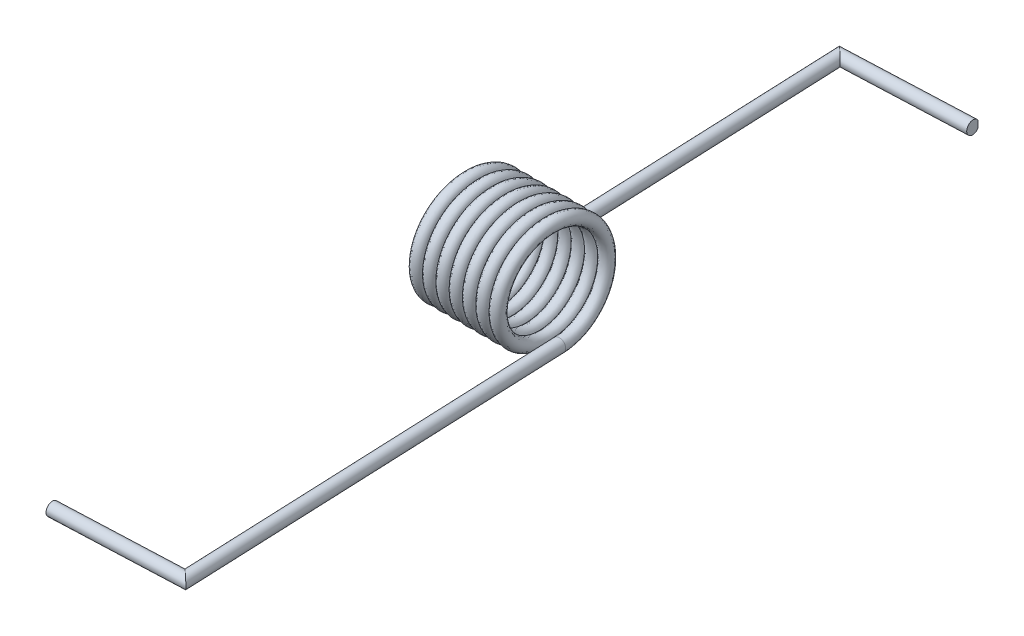
SolidWorks part; units mm, degrees
note: The reader was unsure of these and kept them because the rebuilt part matched: shared geometry of "Sketch16<4>".
ref_plane "Front" through (0, 0, 0) normal (0, 0, 1) x (1, 0, 0)
ref_plane "Top" through (0, 0, 0) normal (0, 1, 0) x (1, 0, 0)
ref_plane "Right" through (0, 0, 0) normal (1, 0, 0) x (0, 0, -1)
sketch "Sketch1" plane through (0, 0, 0) normal (1, 0, 0) x (0, 0, -1)
  line L0 (0, 0) -> (0, -2.2098) construction
  line L1 (0, -2.2098) -> (0, -2.5273) construction
  line L2 (0, -2.5273) -> (0, -2.8448) construction
  circle A0 centre (0, 0) radius 2.2098 construction
  circle A1 centre (0, 0) radius 2.8448 construction
  circle A2 centre (0, 0) radius 2.5273
  circle A3 centre (0, -2.5273) radius 0.3175 construction
  circle A4 centre (0, 0) radius 1.778 construction
curve "Helix/Spiral1" pitch 0.6604 height 4.6228 turns 7
ref_plane "Plane1" through (0, -2.5273, 0) normal (-0.0416, 0, -0.9991) x (-0.9991, 0, 0.0416)
sketch "Sketch2" plane through (0, -2.5273, 0) normal (-0.0416, 0, -0.9991) x (-0.9991, 0, 0.0416)
  circle A0 centre (0, 0) radius 0.3175
sweep "Sweep1" add profiles "Sketch2" path "Helix/Spiral1"
sketch "Sketch3" plane through (0, 0, 0) normal (0.0416, 0, 0.9991) x (0.9991, 0, -0.0416)
  circle A1 centre (0, -2.5273) radius 0.3175
  circle A2 centre (0, -2.5273) radius 0.3175
  dimension "D1" = 0
extrude "Extrude1" add sketch "Sketch3" along normal blind 19.05
sketch "Sketch4" plane through (-0.008, 0, -0.1919) normal (-0.0416, 0, -0.9991) x (-0.9955, -0.0856, 0.0414)
  circle A1 centre (4.8182, -2.1226) radius 0.3175
  circle A2 centre (4.8182, -2.1226) radius 0.3175
  dimension "D1" = 0
extrude "Extrude2" add sketch "Sketch4" along normal blind 19.05
sketch "Sketch7" plane through (0.7916, 0, 19.0335) normal (0.0416, 0, 0.9991) x (0.9991, 0, -0.0416)
  line L1 (0, -2.2098) -> (-6.35, -2.2098)
  line L2 (0, -2.2098) -> (0, -2.8448)
  line L3 (0, -2.8448) -> (-6.35, -2.8448)
  line L4 (-6.35, -2.2098) -> (-6.35, -2.8448)
  circle A0 centre (0, -2.5273) radius 0.3175 construction
  circle A1 centre (0, -2.5273) radius 0.3175 construction
  dimension "D1" = 6.35
extrude "Boss-Extrude1" add sketch "Sketch7" along normal blind 0.635
sketch "Sketch8" plane through (-6.3445, 0, 0.2639) normal (-0.9991, 0, 0.0416) x (0.0416, 0, 0.9991)
  line L2 (19.05, -2.2098) -> (19.685, -2.2098)
  line L3 (19.05, -2.2098) -> (19.05, -2.8448)
  line L4 (19.05, -2.8448) -> (19.685, -2.8448)
  line L5 (19.685, -2.2098) -> (19.685, -2.8448)
  circle A0 centre (19.3675, -2.5273) radius 0.3175
  line M1 (19.05, -2.2098) -> (19.05, -2.8448)
  line M2 (19.05, -2.8448) -> (19.685, -2.8448)
extrude "Cut-Extrude2" cut sketch "Sketch8" against normal up to surface (6.35 mm away) contours A0 L2 M1 | A0 L3 M2 up to face at (0.7916, -2.5273, 19.0335)
sketch "Sketch9" plane through (-6.3445, 0, 0.2639) normal (-0.9991, 0, 0.0416) x (0.0416, 0, 0.9991)
  line L0 (19.3675, -2.2098) -> (19.3675, -2.8448)
  line L1 (19.3675, -2.2098) -> (19.685, -2.2098)
  line L2 (19.685, -2.2098) -> (19.685, -2.8448)
  line L3 (19.685, -2.8448) -> (19.3675, -2.8448)
  circle A0 centre (19.3675, -2.5273) radius 0.3175
  line M2 (19.3675, -2.8448) -> (19.685, -2.8448)
  line M3 (19.685, -2.8448) -> (19.685, -2.2098)
  line M4 (19.685, -2.2098) -> (19.3675, -2.2098)
extrude "Cut-Extrude3" cut sketch "Sketch9" against normal through all contours A0 L2 M4 | A0 M2 M3
sketch "Sketch10" plane through (0.7916, 0, 19.0335) normal (0.0416, 0, 0.9991) x (0.9991, 0, -0.0416)
  line L0 (0, -2.8448) -> (0, -2.2098) construction
  line L1 (0, -2.2098) -> (0, -2.8448)
  circle A0 centre (0, -2.5273) radius 0.3175
  line M1 (0, -2.2098) -> (0, -2.8448)
  arc M2 (0, -2.8448) -> (0, -2.2098) centre (0, -2.5273) ccw
extrude "Boss-Extrude2" add sketch "Sketch10" along normal blind 0.635 contours M2 M1
sketch "Sketch11" plane through (0, 0, 0) normal (-0.9991, 0, 0.0416) x (0.0416, 0, 0.9991)
  line L2 (19.685, -2.5273) -> (19.685, -2.2098)
  line L3 (19.685, -2.2098) -> (19.3675, -2.2098)
  line L4 (19.685, -2.5273) -> (19.685, -2.2098)
  line L5 (19.685, -2.2098) -> (19.3675, -2.2098)
  arc A1 (19.685, -2.5273) -> (19.3675, -2.2098) centre (19.3675, -2.5273) ccw
  arc A2 (19.685, -2.5273) -> (19.3675, -2.2098) centre (19.3675, -2.5273) ccw
  dimension "D1" = 0
extrude "Cut-Extrude4" cut sketch "Sketch11" against normal blind 0.635
sketch "Sketch12" plane through (0, 0, 0) normal (-0.9991, 0, 0.0416) x (0.0416, 0, 0.9991)
  line L0 (19.685, -2.5273) -> (19.685, -2.8448) construction
  line L1 (19.685, -2.8448) -> (19.3675, -2.8448) construction
  line L2 (19.685, -2.5273) -> (19.685, -2.8448)
  line L3 (19.685, -2.8448) -> (19.3675, -2.8448)
  arc A0 (19.3675, -2.8448) -> (19.685, -2.5273) centre (19.3675, -2.5273) ccw construction
  arc A1 (19.3675, -2.8448) -> (19.685, -2.5273) centre (19.3675, -2.5273) ccw
extrude "Cut-Extrude5" cut sketch "Sketch12" against normal blind 0.635
sketch "Sketch13" plane through (-0.7996, 0, -19.2255) normal (-0.0416, 0, -0.9991) x (-0.9991, 0, 0.0416)
  line L1 (4.6188, -2.2098) -> (-1.7312, -2.2098)
  line L2 (4.6188, -2.2098) -> (4.6188, -2.8448)
  line L3 (4.6188, -2.8448) -> (-1.7312, -2.8448)
  line L4 (-1.7312, -2.2098) -> (-1.7312, -2.8448)
  circle A0 centre (4.6188, -2.5273) radius 0.3175 construction
  dimension "D1" = 6.35
extrude "Boss-Extrude3" add sketch "Sketch13" along normal blind 0.635
sketch "Sketch14" plane through (-0.7996, 0, -19.2255) normal (-0.0416, 0, -0.9991) x (-0.9991, 0, 0.0416)
  line L0 (4.6188, -2.8448) -> (4.6188, -2.2098) construction
  line L1 (4.6188, -2.8448) -> (4.6188, -2.2098)
  arc A0 (4.6188, -2.8448) -> (4.6188, -2.2098) centre (4.6188, -2.5273) ccw construction
  arc A1 (4.6188, -2.8448) -> (4.6188, -2.2098) centre (4.6188, -2.5273) ccw
sketch "Sketch16" plane through (1.7297, 0, -0.0719) normal (0.9991, 0, -0.0416) x (-0.0416, 0, -0.9991)
  line L2 (19.2421, -2.2098) -> (19.8771, -2.2098)
  line L3 (19.2421, -2.2098) -> (19.2421, -2.8448)
  line L4 (19.2421, -2.8448) -> (19.8771, -2.8448)
  line L5 (19.8771, -2.2098) -> (19.8771, -2.8448)
  circle A0 centre (19.5596, -2.5273) radius 0.3175
  line M1 (19.2421, -2.2098) -> (19.2421, -2.8448)
  line M2 (19.2421, -2.8448) -> (19.8771, -2.8448)
  line M3 (19.8771, -2.8448) -> (19.8771, -2.2098)
  line M4 (19.8771, -2.2098) -> (19.2421, -2.2098)
extrude "Cut-Extrude7" cut sketch "Sketch16" against normal up to surface (6.35 mm away) contours A0 L2 M1 | A0 L3 M2 up to face at (-5.4144, -2.5273, -19.0335)
extrude "Cut-Extrude8" cut sketch "Sketch16<4>" against normal through all contours A0 L5 M4 | A0 L4 M3
sketch "Sketch16<4>" plane through (1.7297, 0, -0.0719) normal (0.9991, 0, -0.0416) x (-0.0416, 0, -0.9991) same geometry as "Sketch16"
sketch "Sketch17" plane through (-0.7996, 0, -19.2255) normal (-0.0416, 0, -0.9991) x (-0.9991, 0, 0.0416)
  line L1 (4.6188, -2.2098) -> (4.6188, -2.8448)
  line L2 (4.6188, -2.2098) -> (4.6188, -2.8448)
  arc A1 (4.6188, -2.8448) -> (4.6188, -2.2098) centre (4.6188, -2.5273) ccw
  arc A2 (4.6188, -2.8448) -> (4.6188, -2.2098) centre (4.6188, -2.5273) ccw
  dimension "D1" = 0
extrude "Boss-Extrude4" add sketch "Sketch17" along normal blind 2.54
sketch "Sketch18" plane through (-4.6148, 0, 0.1919) normal (0.9991, 0, -0.0416) x (-0.0416, 0, -0.9991)
  line L3 (19.5596, -2.8448) -> (21.7821, -2.8448)
  line L4 (21.7821, -2.8448) -> (21.7821, -2.2098)
  line L5 (21.7821, -2.2098) -> (19.5596, -2.2098)
  line L6 (19.5596, -2.8448) -> (21.7821, -2.8448)
  line L7 (21.7821, -2.8448) -> (21.7821, -2.2098)
  line L8 (21.7821, -2.2098) -> (19.5596, -2.2098)
  arc A1 (19.5596, -2.8448) -> (19.5596, -2.2098) centre (19.5596, -2.5273) ccw
  arc A2 (19.5596, -2.8448) -> (19.5596, -2.2098) centre (19.5596, -2.5273) ccw
  dimension "D1" = 0
extrude "Cut-Extrude9" cut sketch "Sketch18" against normal blind 2.54
sketch "Sketch19" plane through (1.7297, 0, -0.0719) normal (0.9991, 0, -0.0416) x (-0.0416, 0, -0.9991)
  line L0 (19.8266, -2.3555) -> (19.8266, -2.6991)
  line L1 (19.8266, -2.3555) -> (20.0248, -2.3433)
  line L2 (20.0248, -2.3433) -> (19.9514, -2.7674)
  line L3 (19.9514, -2.7674) -> (19.8266, -2.6991)
  circle A0 centre (19.5596, -2.5273) radius 0.3175 construction
  circle A1 centre (19.5596, -2.5273) radius 0.3175
  circle M2 centre (19.5596, -2.5273) radius 0.3175
extrude "Cut-Extrude10" cut sketch "Sketch19" against normal blind 1 contours L0 M2
equation "\"D1@Extrude2\"=\"Leg Length@Extrude1\""
